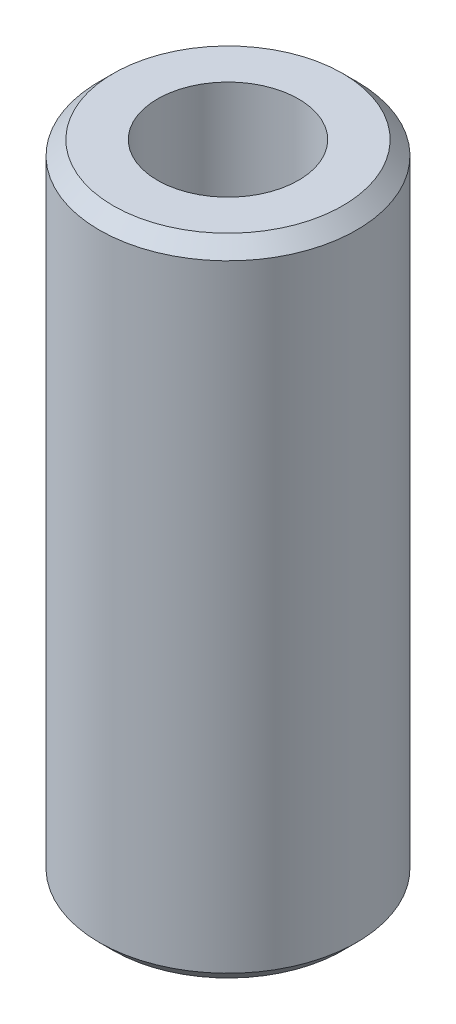
SolidWorks part; units mm, degrees
ref_plane "Front Plane" through (0, 0, 0) normal (0, 0, 1) x (1, 0, 0)
ref_plane "Top Plane" through (0, 0, 0) normal (0, 1, 0) x (1, 0, 0)
ref_plane "Right Plane" through (0, 0, 0) normal (1, 0, 0) x (0, 0, -1)
sketch "Sketch1" plane through (0, 0, 0) normal (0, 1, 0) x (1, 0, 0)
  circle A0 centre (0, 0) radius 25
  dimension "SHAFT_OD" = 50
extrude "Boss-Extrude1" add sketch "Sketch1" along normal blind 125.3069
sketch "Sketch2" plane through (0, 0, 0) normal (0, 1, 0) x (1, 0, 0)
  circle A0 centre (0, 0) radius 13.7051
  dimension "BORE_D" = 27.4102
extrude "Cut-Extrude1" cut sketch "Sketch2" along normal through all
chamfer "Chamfer1" distance 2.7211 angle 45 2 edges at (0, 125.3069, 25) (0, 0, 25)
